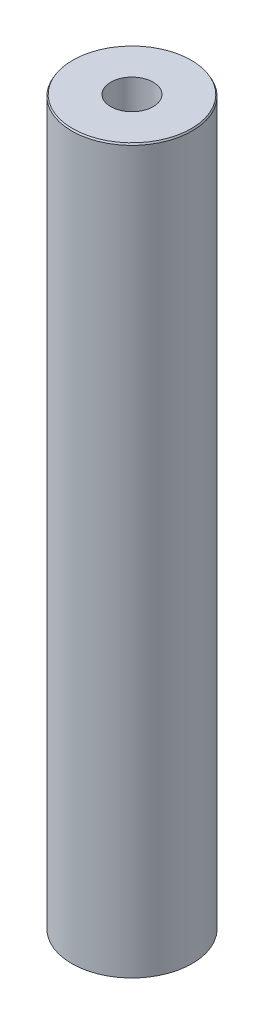
SolidWorks part; units mm, degrees
ref_plane "Front Plane" through (0, 0, 0) normal (0, 0, 1) x (1, 0, 0)
ref_plane "Top Plane" through (0, 0, 0) normal (0, 1, 0) x (1, 0, 0)
ref_plane "Right Plane" through (0, 0, 0) normal (1, 0, 0) x (0, 0, -1)
sketch "Sketch1" plane through (0, 0, 0) normal (0, 1, 0) x (1, 0, 0)
  circle A0 centre (0, 0) radius 27.5
  dimension "SHAFT_OD" = 55
extrude "Boss-Extrude1" add sketch "Sketch1" along normal blind 330.4942
sketch "Sketch2" plane through (0, 0, 0) normal (0, 1, 0) x (1, 0, 0)
  circle A0 centre (0, 0) radius 9.6984
  dimension "BORE_D" = 19.3968
extrude "Cut-Extrude1" cut sketch "Sketch2" along normal through all
chamfer "Chamfer1" distance 0.7252 angle 30 2 edges at (0, 330.4942, 27.5) (0, 0, 27.5) first distance on face at (0, 330.4942, 27.5) first distance on face at (0, 0, 9.6984)
